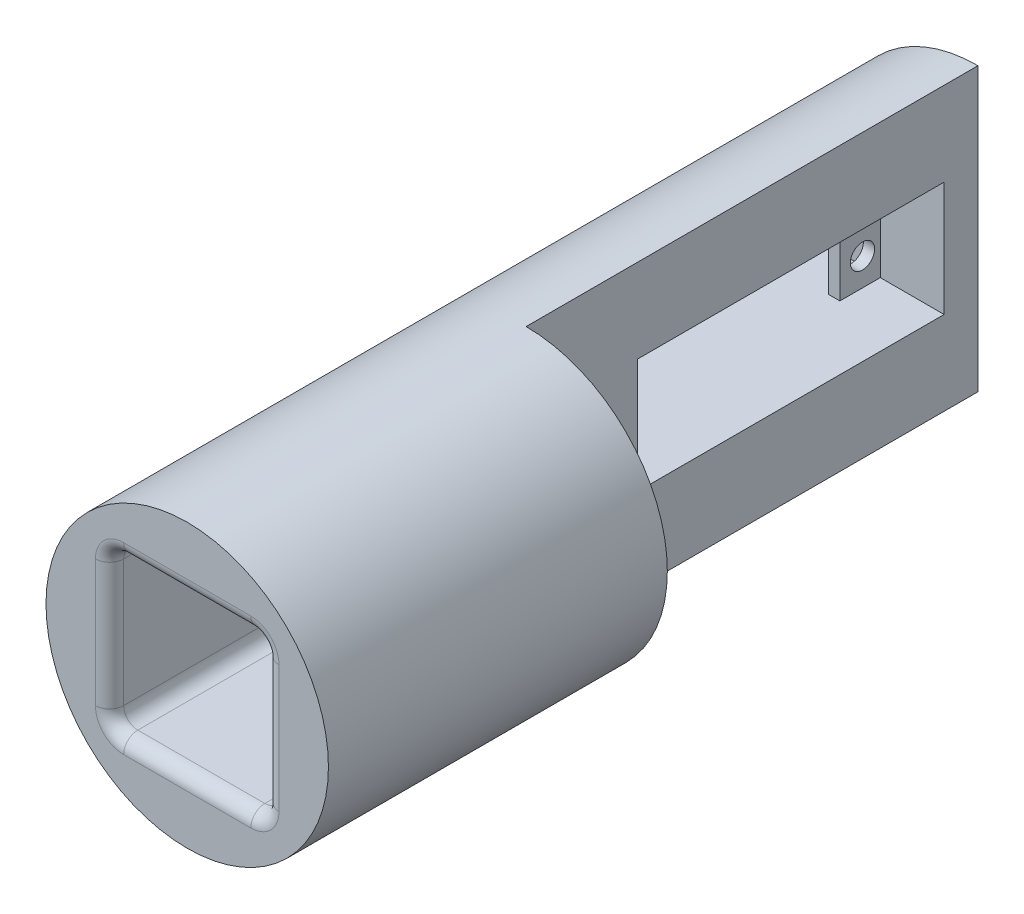
SolidWorks part; units mm, degrees
material "Custom Plastic"
ref_plane "Front Plane" through (0, 0, 0) normal (0, 0, 1) x (1, 0, 0)
ref_plane "Top Plane" through (0, 0, 0) normal (0, 1, 0) x (1, 0, 0)
ref_plane "Right Plane" through (0, 0, 0) normal (1, 0, 0) x (0, 0, -1)
sketch "Sketch1" plane through (0, 0, 0) normal (0, 0, 1) x (1, 0, 0)
  line L0 (-13.75, 13.75) -> (13.75, -13.75) construction
  line L1 (-13.75, 13.75) -> (13.75, 13.75)
  line L2 (-13.75, 13.75) -> (-13.75, -13.75)
  line L3 (-13.75, -13.75) -> (13.75, -13.75)
  line L4 (13.75, 13.75) -> (13.75, -13.75)
  circle A0 centre (0, 0) radius 25
  point P7 (0, 0)
  dimension "D2" = 50
  dimension "2.75" = 27.5
extrude "Boss-Extrude1" add sketch "Sketch1" along normal blind 55
sketch "Sketch2" plane through (0, 0, 0) normal (0, 0, -1) x (-1, 0, 0)
  circle A0 centre (0, 0) radius 25
  circle A1 centre (0, 0) radius 25
  circle A2 centre (0, 0) radius 25
  circle M2 centre (0, 0) radius 25
  line M3 (13.75, 13.75) -> (13.75, -13.75)
  line M4 (13.75, -13.75) -> (-13.75, -13.75)
  line M5 (-13.75, -13.75) -> (-13.75, 13.75)
  line M6 (-13.75, 13.75) -> (13.75, 13.75)
  dimension "D1" = 0
extrude "Boss-Extrude2" add sketch "Sketch2" along normal blind 5 contours M2 M6 M3 M4 M5 | M3 M6 M5 M4 region at (24.2929, 0, 0) region at (0, 0, 0)
sketch "Sketch3" plane through (0, 0, -5) normal (0, 0, -1) x (-1, 0, 0)
  line L1 (0, 25) -> (25, 25)
  line L2 (0, 25) -> (0, -25)
  line L3 (0, -25) -> (25, -25)
  line L4 (25, 25) -> (25, -25)
  circle A0 centre (0, 0) radius 25 construction
extrude "Boss-Extrude3" add sketch "Sketch3" along normal blind 80
ref_plane "Plane1" through (0, 0, -5) normal (0, 0, 1) x (1, 0, 0)
fillet "Fillet1" radius 2.5 4 edges at (-13.75, 13.75, 27.5) (13.75, 13.75, 27.5) (-13.75, -13.75, 27.5) (13.75, -13.75, 27.5)
fillet "Fillet2" radius 2.5 1 edges at (13.75, 0, 55) type face fillet first side face at (25, 0, 55) second side face at (13.75, 0, 27.5)
ref_plane "Plane2" through (-50, 0, 0) normal (-1, 0, 0) x (0, 0, 1)
sketch "Sketch18" plane through (0, 0, -5) normal (0, 0, 1) x (1, 0, 0)
  line L0 (0, -25) -> (-25, -25)
  line L1 (-25, 0) -> (-25, 25)
  line L2 (-25, -25) -> (0, -25)
  line L3 (-25, 0) -> (-25, -25)
  line L4 (-25, -25) -> (0, -25)
  line L5 (-25, 0) -> (-25, -25)
  line L6 (-25, 25) -> (0, 25)
  arc A1 (-25, 0) -> (0, -25) centre (0, 0) ccw
  arc A2 (-25, 0) -> (0, -25) centre (0, 0) ccw
  circle A3 centre (0, 0) radius 25
  circle A4 centre (0, 0) radius 25
  line M5 (-25, 25) -> (-25, 0)
  arc M6 (-25, 0) -> (0, 25) centre (0, 0) cw
  line M7 (0, 25) -> (-25, 25)
  dimension "D1" = 0
  dimension "D2" = 0
sketch "Sketch21" plane through (0, 0, 0) normal (1, 0, 0) x (0, 0, -1)
  line L0 (24.7, 10.15) -> (79, 10.15)
  line L1 (79, 10.15) -> (79, -10.15)
  line L2 (79, -10.15) -> (24.7, -10.15)
  line L3 (24.7, -10.15) -> (24.7, 10.15)
  line L6 (85, 25) -> (85, -25) construction
  line L7 (51.85, -10.15) -> (51.85, -25)
  line L8 (85, -25) -> (5, -25) construction
  line L9 (51.85, 10.15) -> (51.85, 25)
  line L10 (85, 25) -> (5, 25) construction
  dimension "D1" = 6
  dimension "D2" = 54.3
  dimension "D3" = 20.3
extrude "Cut-Extrude1" cut sketch "Sketch21" against normal blind 11.3 contours L3 L0 L1 L2
sketch "Sketch22" plane through (0, 0, 0) normal (1, 0, 0) x (0, 0, -1)
  line L0 (31.55, 10.15) -> (71.85, 10.15)
  line L1 (24.7, 10.15) -> (79, 10.15) construction
  line L2 (71.85, 10.15) -> (71.85, -10.15)
  line L3 (79, -10.15) -> (24.7, -10.15) construction
  line L4 (71.85, -10.15) -> (31.55, -10.15)
  line L5 (31.55, 10.15) -> (31.55, -10.15)
  line M9 (79, -10.15) -> (24.7, -10.15)
  line M11 (24.7, 10.15) -> (79, 10.15)
  dimension "D1" = 40.3
extrude "Cut-Extrude2" cut sketch "Sketch22" against normal through all contours L5 L2 M11 M9 region at (0, 0, -51.7)
extrude "Cut-Extrude3" cut sketch "Sketch18" against normal through all contours A2 L5 L0 | M7 M5 M6 region at (-19.4158, -19.4158, -5) region at (-19.4158, 19.4158, -5)
sketch "Sketch23" plane through (0, 0, 0) normal (1, 0, 0) x (0, 0, -1)
  line L0 (27.85, 5.25) -> (27.85, -5.25) construction
  line L1 (27.85, -5.25) -> (75.85, -5.25) construction
  line L2 (75.85, -5.25) -> (75.85, 5.25) construction
  line L3 (75.85, 5.25) -> (27.85, 5.25) construction
  circle A0 centre (75.85, 5.25) radius 2.15
  circle A1 centre (75.85, -5.25) radius 2.15
  circle A3 centre (27.85, 5.25) radius 2.15
  circle A4 centre (27.85, -5.25) radius 2.15
  dimension "D1" = 4.3
extrude "Cut-Extrude4" cut sketch "Sketch23" against normal through all contours A4 | A0 | A1 | A3 region at (0, 5.25, -75.85) region at (0, -5.25, -75.85) region at (0, -5.25, -27.85)
ref_plane "Plane3" through (0, 0, -51.7) normal (0, 0, -1) x (-1, 0, 0)
sketch "Sketch24" plane through (0, 0, -51.7) normal (0, 0, -1) x (-1, 0, 0)
  line L0 (13.3, 10.15) -> (13.3, -10.15)
  line L7 (22.8468, 10.15) -> (11.3, 10.15)
  line L8 (11.3, 10.15) -> (11.3, -10.15)
  line L9 (11.3, -10.15) -> (22.8468, -10.15)
  line L13 (22.8468, 10.15) -> (13.3, 10.15)
  line L15 (13.3, -10.15) -> (22.8468, -10.15)
  arc A2 (22.8468, -10.15) -> (22.8468, 10.15) centre (0, 0) ccw
  arc A4 (22.8468, -10.15) -> (22.8468, 10.15) centre (0, 0) ccw
  dimension "D1" = 0
  dimension "D2" = 13.3
extrude "Cut-Extrude7" cut sketch "Sketch24" against normal mid plane 55
